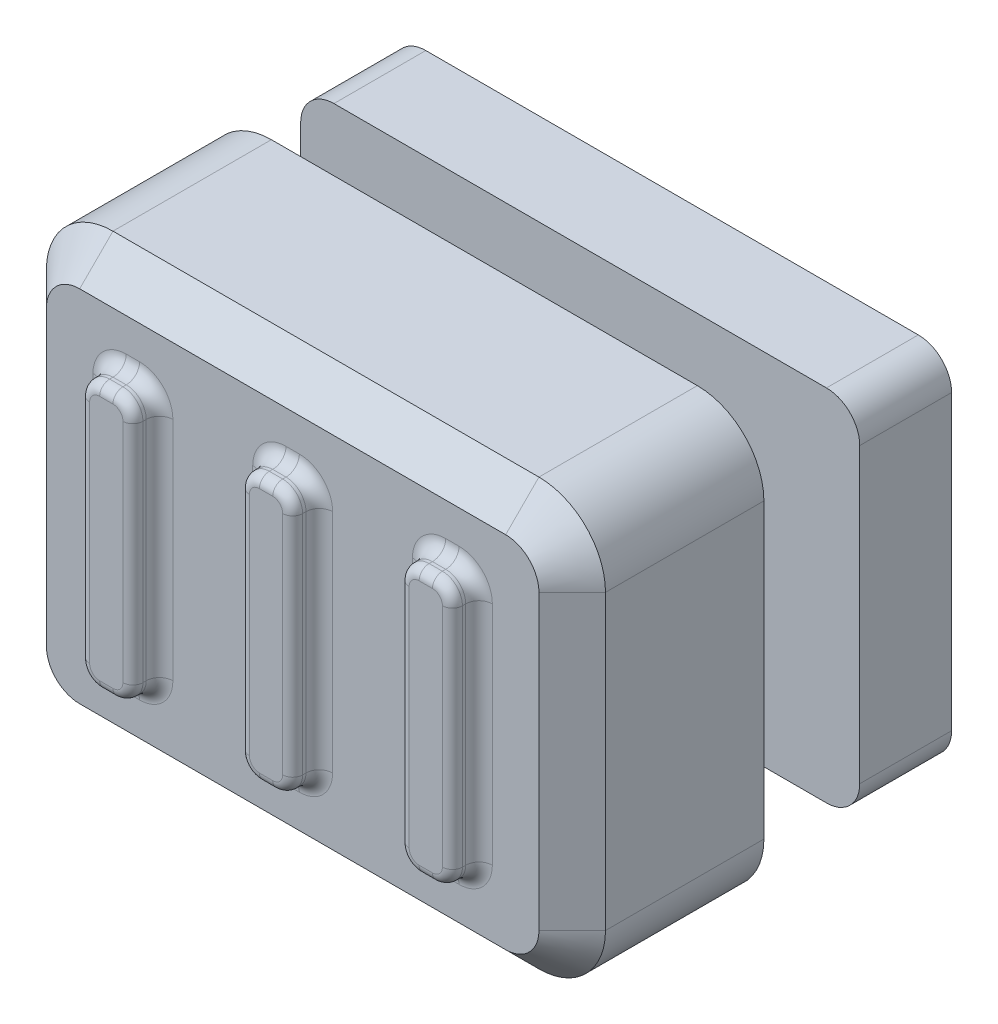
SolidWorks part; units mm, degrees
ref_plane "Спереди" through (0, 0, 0) normal (0, 0, 1) x (1, 0, 0)
ref_plane "Сверху" through (0, 0, 0) normal (0, 1, 0) x (1, 0, 0)
ref_plane "Справа" through (0, 0, 0) normal (1, 0, 0) x (0, 0, -1)
other "Configuration Table"
sketch "Slider_stem_profile" plane through (0, 0, 0) normal (0, 0, 1) x (1, 0, 0)
  line L0 (-1.5, -1.5) -> (1.5, -1.5)
  line L1 (1.9, -1.1) -> (1.9, 1.1)
  line L2 (1.5, 1.5) -> (-1.5, 1.5)
  line L3 (-1.9, 1.1) -> (-1.9, -1.1)
  arc A0 (1.5, -1.5) -> (1.9, -1.1) centre (1.5, -1.1) ccw
  arc A1 (1.9, 1.1) -> (1.5, 1.5) centre (1.5, 1.1) ccw
  arc A2 (-1.5, 1.5) -> (-1.9, 1.1) centre (-1.5, 1.1) ccw
  arc A3 (-1.9, -1.1) -> (-1.5, -1.5) centre (-1.5, -1.1) ccw
extrude "Slider_stem" add sketch "Slider_stem_profile" along normal blind 4.2 from offset 0
sketch "Captive_flange_profile" plane through (0, 0, 0) normal (0, 0, 1) x (1, 0, 0)
  line L0 (-3.7, -2.7) -> (3.7, -2.7)
  line L1 (4.2, -2.2) -> (4.2, 2.2)
  line L2 (3.7, 2.7) -> (-3.7, 2.7)
  line L3 (-4.2, 2.2) -> (-4.2, -2.2)
  arc A0 (3.7, -2.7) -> (4.2, -2.2) centre (3.7, -2.2) ccw
  arc A1 (4.2, 2.2) -> (3.7, 2.7) centre (3.7, 2.2) ccw
  arc A2 (-3.7, 2.7) -> (-4.2, 2.2) centre (-3.7, 2.2) ccw
  arc A3 (-4.2, -2.2) -> (-3.7, -2.7) centre (-3.7, -2.2) ccw
extrude "Captive_flange" add sketch "Captive_flange_profile" along normal blind 1.38 from offset 1.2
sketch "Thumb_pad_profile" plane through (0, 0, 0) normal (0, 0, 1) x (1, 0, 0)
  line L0 (-3.2, -3.2) -> (3.2, -3.2)
  line L1 (4.2, -2.2) -> (4.2, 2.2)
  line L2 (3.2, 3.2) -> (-3.2, 3.2)
  line L3 (-4.2, 2.2) -> (-4.2, -2.2)
  arc A0 (3.2, -3.2) -> (4.2, -2.2) centre (3.2, -2.2) ccw
  arc A1 (4.2, 2.2) -> (3.2, 3.2) centre (3.2, 2.2) ccw
  arc A2 (-3.2, 3.2) -> (-4.2, 2.2) centre (-3.2, 2.2) ccw
  arc A3 (-4.2, -2.2) -> (-3.2, -3.2) centre (-3.2, -2.2) ccw
extrude "Thumb_pad" add sketch "Thumb_pad_profile" along normal blind 2.38 from offset 4.02
ref_plane "Thumb_pad_chamfer_plane_0" through (0, 0, 6.4) normal (0, 0, 1) x (1, 0, 0)
sketch "Thumb_pad_chamfer_section_0" plane through (0, 0, 6.4) normal (0, 0, 1) x (1, 0, 0)
  line L0 (-3.2, -3.2) -> (3.2, -3.2)
  line L1 (4.2, -2.2) -> (4.2, 2.2)
  line L2 (3.2, 3.2) -> (-3.2, 3.2)
  line L3 (-4.2, 2.2) -> (-4.2, -2.2)
  arc A0 (3.2, -3.2) -> (4.2, -2.2) centre (3.2, -2.2) ccw
  arc A1 (4.2, 2.2) -> (3.2, 3.2) centre (3.2, 2.2) ccw
  arc A2 (-3.2, 3.2) -> (-4.2, 2.2) centre (-3.2, 2.2) ccw
  arc A3 (-4.2, -2.2) -> (-3.2, -3.2) centre (-3.2, -2.2) ccw
ref_plane "Thumb_pad_chamfer_plane_1" through (0, 0, 6.9) normal (0, 0, 1) x (1, 0, 0)
sketch "Thumb_pad_chamfer_section_1" plane through (0, 0, 6.9) normal (0, 0, 1) x (1, 0, 0)
  line L0 (-3.2, -2.7) -> (3.2, -2.7)
  line L1 (3.7, -2.2) -> (3.7, 2.2)
  line L2 (3.2, 2.7) -> (-3.2, 2.7)
  line L3 (-3.7, 2.2) -> (-3.7, -2.2)
  arc A0 (3.2, -2.7) -> (3.7, -2.2) centre (3.2, -2.2) ccw
  arc A1 (3.7, 2.2) -> (3.2, 2.7) centre (3.2, 2.2) ccw
  arc A2 (-3.2, 2.7) -> (-3.7, 2.2) centre (-3.2, 2.2) ccw
  arc A3 (-3.7, -2.2) -> (-3.2, -2.7) centre (-3.2, -2.2) ccw
loft "Thumb_pad_chamfer" add profiles "Thumb_pad_chamfer_section_0", "Thumb_pad_chamfer_section_1"
sketch "Switch_pin_socket_profile" plane through (0, 0, 0) normal (0, 0, 1) x (1, 0, 0)
  line L0 (-0.725, -0.6) -> (0.725, -0.6)
  line L1 (0.825, -0.5) -> (0.825, 0.5)
  line L2 (0.725, 0.6) -> (-0.725, 0.6)
  line L3 (-0.825, 0.5) -> (-0.825, -0.5)
  arc A0 (0.725, -0.6) -> (0.825, -0.5) centre (0.725, -0.5) ccw
  arc A1 (0.825, 0.5) -> (0.725, 0.6) centre (0.725, 0.5) ccw
  arc A2 (-0.725, 0.6) -> (-0.825, 0.5) centre (-0.725, 0.5) ccw
  arc A3 (-0.825, -0.5) -> (-0.725, -0.6) centre (-0.725, -0.5) ccw
extrude "Switch_pin_socket" cut sketch "Switch_pin_socket_profile" against normal blind 2.4 from offset 2.3
sketch "PCB_edge_relief_profile" plane through (0, 0, 0) normal (0, 0, 1) x (1, 0, 0)
  line L0 (-2, 0.55) -> (2, 0.55)
  line L1 (2, 0.55) -> (2, 1.6)
  line L2 (2, 1.6) -> (-2, 1.6)
  line L3 (-2, 1.6) -> (-2, 0.55)
extrude "PCB_edge_relief" cut sketch "PCB_edge_relief_profile" against normal blind 0.7 from offset 0.6
fillet "Stem_shoulder_round" radius 0.2 24 edges at (1.7828, -1.3828, 1.2) (-1.7828, -1.3828, 1.2) (-1.7828, 1.3828, 1.2) (1.7828, 1.3828, 1.2) (1.7828, -1.3828, 2.58) (-1.7828, -1.3828, 2.58) (-1.7828, 1.3828, 2.58) (1.7828, 1.3828, 2.58) (1.7828, -1.3828, 4.02) (-1.7828, -1.3828, 4.02) (-1.7828, 1.3828, 4.02) (1.7828, 1.3828, 4.02) (0, 1.5, 1.2) (-1.9, 0, 1.2) (0, -1.5, 1.2) (1.9, 0, 1.2) (0, 1.5, 2.58) (-1.9, 0, 2.58) (0, -1.5, 2.58) (1.9, 0, 2.58) (0, 1.5, 4.02) (-1.9, 0, 4.02) (0, -1.5, 4.02) (1.9, 0, 4.02)
sketch "Thumb_rib_0_profile" plane through (0, 0, 0) normal (0, 0, 1) x (1, 0, 0)
  line L0 (-2.5, -2) -> (-2.3, -2)
  line L1 (-2, -1.7) -> (-2, 1.7)
  line L2 (-2.3, 2) -> (-2.5, 2)
  line L3 (-2.8, 1.7) -> (-2.8, -1.7)
  arc A0 (-2.3, -2) -> (-2, -1.7) centre (-2.3, -1.7) ccw
  arc A1 (-2, 1.7) -> (-2.3, 2) centre (-2.3, 1.7) ccw
  arc A2 (-2.5, 2) -> (-2.8, 1.7) centre (-2.5, 1.7) ccw
  arc A3 (-2.8, -1.7) -> (-2.5, -2) centre (-2.5, -1.7) ccw
extrude "Thumb_rib_0" add sketch "Thumb_rib_0_profile" along normal blind 0.5 from offset 6.8
sketch "Thumb_rib_1_profile" plane through (0, 0, 0) normal (0, 0, 1) x (1, 0, 0)
  line L0 (-0.1, -2) -> (0.1, -2)
  line L1 (0.4, -1.7) -> (0.4, 1.7)
  line L2 (0.1, 2) -> (-0.1, 2)
  line L3 (-0.4, 1.7) -> (-0.4, -1.7)
  arc A0 (0.1, -2) -> (0.4, -1.7) centre (0.1, -1.7) ccw
  arc A1 (0.4, 1.7) -> (0.1, 2) centre (0.1, 1.7) ccw
  arc A2 (-0.1, 2) -> (-0.4, 1.7) centre (-0.1, 1.7) ccw
  arc A3 (-0.4, -1.7) -> (-0.1, -2) centre (-0.1, -1.7) ccw
extrude "Thumb_rib_1" add sketch "Thumb_rib_1_profile" along normal blind 0.5 from offset 6.8
sketch "Thumb_rib_2_profile" plane through (0, 0, 0) normal (0, 0, 1) x (1, 0, 0)
  line L0 (2.3, -2) -> (2.5, -2)
  line L1 (2.8, -1.7) -> (2.8, 1.7)
  line L2 (2.5, 2) -> (2.3, 2)
  line L3 (2, 1.7) -> (2, -1.7)
  arc A0 (2.5, -2) -> (2.8, -1.7) centre (2.5, -1.7) ccw
  arc A1 (2.8, 1.7) -> (2.5, 2) centre (2.5, 1.7) ccw
  arc A2 (2.3, 2) -> (2, 1.7) centre (2.3, 1.7) ccw
  arc A3 (2, -1.7) -> (2.3, -2) centre (2.3, -1.7) ccw
extrude "Thumb_rib_2" add sketch "Thumb_rib_2_profile" along normal blind 0.5 from offset 6.8
fillet "Thumb_rib_root_round" radius 0.2 24 edges at (-0.3121, -1.9121, 6.9) (0, -2, 6.9) (0.3121, -1.9121, 6.9) (0.3121, 1.9121, 6.9) (0, 2, 6.9) (-0.3121, 1.9121, 6.9) (2.0879, -1.9121, 6.9) (2.4, -2, 6.9) (2.7121, -1.9121, 6.9) (2.7121, 1.9121, 6.9) (2.4, 2, 6.9) (2.0879, 1.9121, 6.9) (-2.7121, -1.9121, 6.9) (-2.4, -2, 6.9) (-2.0879, -1.9121, 6.9) (-2.0879, 1.9121, 6.9) (-2.4, 2, 6.9) (-2.7121, 1.9121, 6.9) (0.4, 0, 6.9) (-0.4, 0, 6.9) (2.8, 0, 6.9) (2, 0, 6.9) (-2, 0, 6.9) (-2.8, 0, 6.9)
fillet "Thumb_rib_crown_round" radius 0.15 24 edges at (0.4, 0, 7.3) (0.3121, 1.9121, 7.3) (0.3121, -1.9121, 7.3) (0, 2, 7.3) (0, -2, 7.3) (-0.3121, 1.9121, 7.3) (-0.3121, -1.9121, 7.3) (-0.4, 0, 7.3) (2.8, 0, 7.3) (2.7121, 1.9121, 7.3) (2.7121, -1.9121, 7.3) (2.4, 2, 7.3) (2.4, -2, 7.3) (2.0879, 1.9121, 7.3) (2.0879, -1.9121, 7.3) (2, 0, 7.3) (-2, 0, 7.3) (-2.0879, 1.9121, 7.3) (-2.0879, -1.9121, 7.3) (-2.4, 2, 7.3) (-2.4, -2, 7.3) (-2.7121, 1.9121, 7.3) (-2.7121, -1.9121, 7.3) (-2.8, 0, 7.3)
